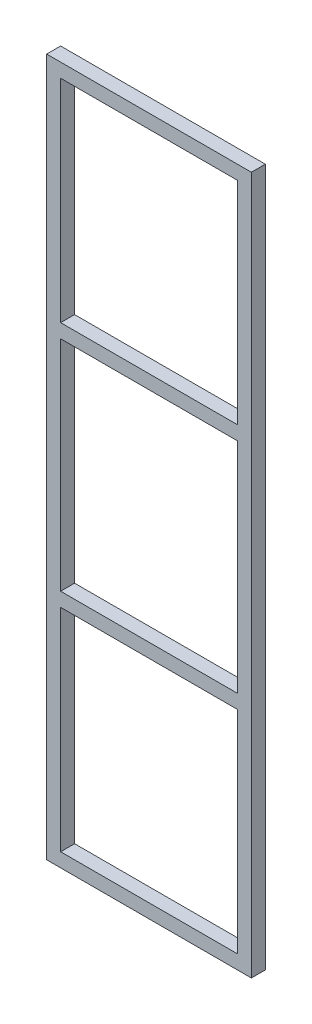
SolidWorks part; units mm, degrees
ref_plane "Front Plane" through (0, 0, 0) normal (0, 0, 1) x (1, 0, 0)
ref_plane "Top Plane" through (0, 0, 0) normal (0, 1, 0) x (1, 0, 0)
ref_plane "Right Plane" through (0, 0, 0) normal (1, 0, 0) x (0, 0, -1)
sketch "Sketch1" plane through (0, 0, 0) normal (0, 0, 1) x (1, 0, 0)
  line L0 (44, 144) -> (44, 53)
  line L9 (-38, -150) -> (50, -150)
  line L10 (-38, -150) -> (-38, 150)
  line L11 (-38, 150) -> (50, 150)
  line L12 (50, -150) -> (50, 150)
  line L15 (-32, -144) -> (44, -144)
  line L16 (-32, -144) -> (-32, -53)
  line L17 (-32, 144) -> (44, 144)
  line L21 (-32, 53) -> (44, 53)
  line L23 (-32, 47) -> (44, 47)
  line L25 (-32, -47) -> (44, -47)
  line L27 (-32, -53) -> (44, -53)
  line L33 (44, 47) -> (44, -47)
  line L34 (-32, 53) -> (-32, 144)
  line L35 (-32, -47) -> (-32, 47)
  line L36 (44, -53) -> (44, -144)
  point P0 (0, 0)
  point P6 (0, 0)
  point P20 (0, 0)
  dimension "D1" = 88
  dimension "D2" = 300
  dimension "D3" = 76
  dimension "D4" = 288
  dimension "D5" = 6
  dimension "D6" = 91
  dimension "D7" = 6
  dimension "D8" = 91
extrude "Boss-Extrude1" add sketch "Sketch1" along normal blind 6
